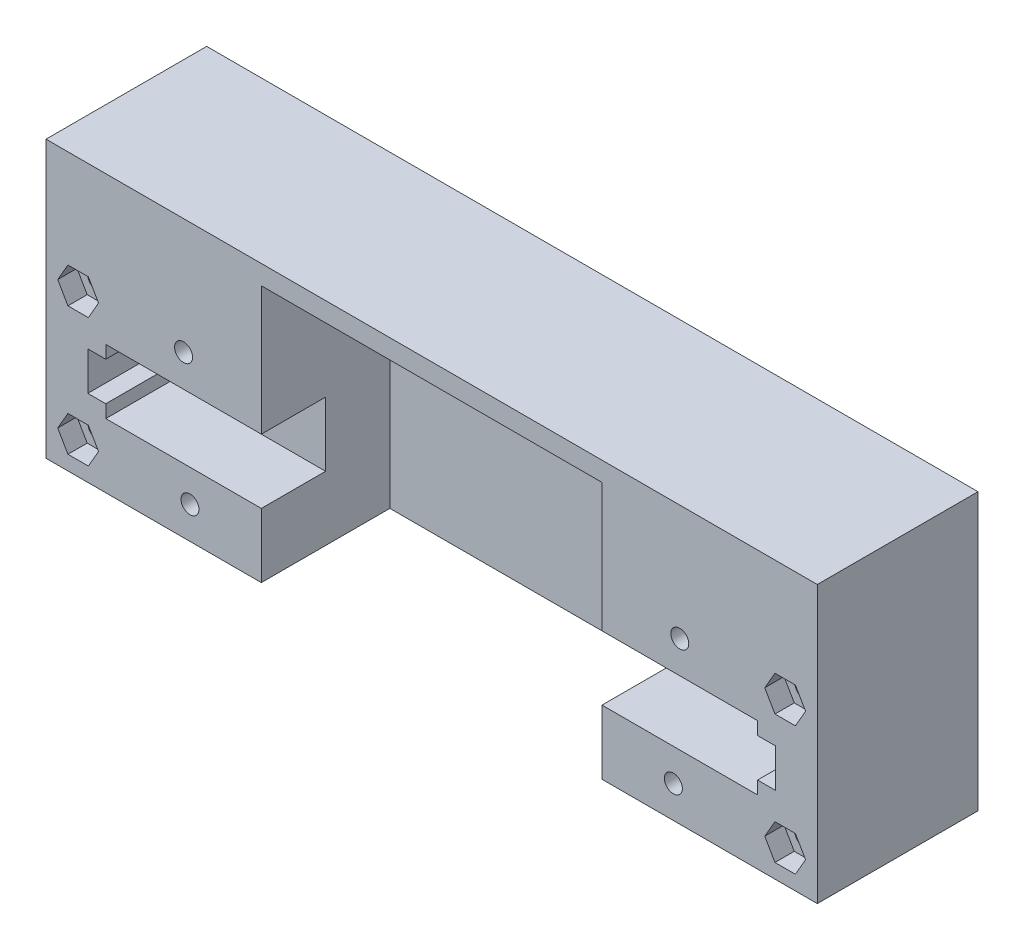
SolidWorks part; units mm, degrees
note: The reader was unsure of these and kept them because the rebuilt part matched: shared geometry of "Esquisse1<4>", "Esquisse1<5>", "Esquisse1<6>".
ref_plane "Plan de face" through (0, 0, 0) normal (0, 0, 1) x (1, 0, 0)
ref_plane "Plan de dessus" through (0, 0, 0) normal (0, 1, 0) x (1, 0, 0)
ref_plane "Plan de droite" through (0, 0, 0) normal (1, 0, 0) x (0, 0, -1)
sketch "Esquisse1" plane through (0, 0, 0) normal (0, 0, 1) x (1, 0, 0)
  line L0 (-60, 0) -> (60, 0) construction
  line L1 (-60, 15) -> (60, 15)
  line L2 (-60, 15) -> (-60, -15)
  line L3 (-60, -15) -> (60, -15)
  line L4 (60, 15) -> (60, -15)
  line L5 (-60, 15) -> (60, -15) construction
  line L6 (-60, -15) -> (60, 15) construction
  line L7 (60, 5) -> (-60, 5)
  line L8 (60, 5) -> (60, -5)
  line L9 (60, -5) -> (-60, -5)
  line L10 (-60, 5) -> (-60, -5)
  line L11 (60, 5) -> (-60, -5) construction
  line L12 (60, -5) -> (-60, 5) construction
  line L13 (26.5, 15) -> (-26.5, 15)
  line L14 (26.5, 15) -> (26.5, -15)
  line L15 (26.5, -15) -> (-26.5, -15)
  line L16 (-26.5, 15) -> (-26.5, -15)
  line L17 (26.5, 15) -> (-26.5, -15) construction
  line L18 (26.5, -15) -> (-26.5, 15) construction
  line L19 (-60, 5) -> (-53.5, 5)
  line L20 (-60, 5) -> (-60, -5)
  line L21 (-60, -5) -> (-53.5, -5)
  line L22 (-53.5, 5) -> (-53.5, -5)
  line L23 (60, 5) -> (53.5, 5)
  line L24 (60, 5) -> (60, -5)
  line L25 (60, -5) -> (53.5, -5)
  line L26 (53.5, 5) -> (53.5, -5)
  line L27 (-53.5, 5) -> (-50.7, 5)
  line L28 (-53.5, 5) -> (-53.5, 3)
  line L29 (-53.5, 3) -> (-50.7, 3)
  line L30 (-50.7, 5) -> (-50.7, 3)
  line L31 (-53.5, -3) -> (-50.7, -3)
  line L32 (-53.5, -3) -> (-53.5, -5)
  line L33 (-53.5, -5) -> (-50.7, -5)
  line L34 (-50.7, -3) -> (-50.7, -5)
  line L35 (53.5, 5) -> (50.7, 5)
  line L36 (53.5, 5) -> (53.5, 3)
  line L37 (53.5, 3) -> (50.7, 3)
  line L38 (50.7, 5) -> (50.7, 3)
  line L39 (53.5, -5) -> (50.7, -5)
  line L40 (53.5, -5) -> (53.5, -3)
  line L41 (53.5, -3) -> (50.7, -3)
  line L42 (50.7, -5) -> (50.7, -3)
  line L43 (0, 15) -> (0, -15) construction
  line L44 (-53.4123, -7.25) -> (-51.8246, -10)
  line L45 (-51.8246, 10) -> (-53.4123, 12.75)
  line L46 (-53.4123, 12.75) -> (-56.5877, 12.75)
  line L47 (-56.5877, 12.75) -> (-58.1754, 10)
  line L48 (-58.1754, 10) -> (-56.5877, 7.25)
  line L49 (-56.5877, 7.25) -> (-53.4123, 7.25)
  line L50 (-53.4123, 7.25) -> (-51.8246, 10)
  line L51 (-56.5877, -7.25) -> (-53.4123, -7.25)
  line L52 (-58.1754, -10) -> (-56.5877, -7.25)
  line L53 (-56.5877, -12.75) -> (-58.1754, -10)
  line L54 (-53.4123, -12.75) -> (-56.5877, -12.75)
  line L55 (-51.8246, -10) -> (-53.4123, -12.75)
  line L56 (56.5877, -7.25) -> (53.4123, -7.25)
  line L57 (58.1754, -10) -> (56.5877, -7.25)
  line L58 (56.5877, -12.75) -> (58.1754, -10)
  line L59 (53.4123, -12.75) -> (56.5877, -12.75)
  line L60 (51.8246, -10) -> (53.4123, -12.75)
  line L61 (53.4123, -7.25) -> (51.8246, -10)
  line L62 (53.4123, 7.25) -> (51.8246, 10)
  line L63 (56.5877, 7.25) -> (53.4123, 7.25)
  line L64 (58.1754, 10) -> (56.5877, 7.25)
  line L65 (56.5877, 12.75) -> (58.1754, 10)
  line L66 (53.4123, 12.75) -> (56.5877, 12.75)
  line L67 (51.8246, 10) -> (53.4123, 12.75)
  circle A0 centre (-55, 10) radius 1.5
  circle A1 centre (-55, -10) radius 1.5
  circle A2 centre (55, -10) radius 1.5
  circle A3 centre (55, 10) radius 1.5
  circle A4 centre (-55, 10) radius 2.75 construction
  circle A5 centre (-55, -10) radius 2.75 construction
  circle A6 centre (55, -10) radius 2.75 construction
  circle A7 centre (55, 10) radius 2.75 construction
  point P0 (0, 0)
  point P6 (0, 0)
  point P11 (0, 0)
  dimension "D9" = 55
  dimension "D11" = 3
  dimension "D1" = 120
  dimension "D2" = 30
  dimension "D3" = 10
  dimension "D4" = 53
  dimension "D5" = 27
  dimension "D6" = 27
  dimension "D7" = 24.2
  dimension "D8" = 2
  dimension "D10" = 10
extrude "Boss.-Extru.1" add sketch "Esquisse1" against normal blind 5 contours L1 L4 L3 L2 | A0 | A1 | A2 | A3
extrude "Boss.-Extru.2" add sketch "Esquisse1<4>" along normal blind 20 contours L16 L1 L2 L7 | L16 L9 L2 L3 | L9 L14 L3 L4 | L1 L14 L7 L4 | L22 L7 L2 L9 | L7 L26 L9 L4 | L28 L27 L30 L29 | L32 L31 L34 L33 | L40 L39 L42 L41 | L36 L35 L38 L37
sketch "Esquisse1<4>" plane through (0, 0, 0) normal (0, 0, 1) x (1, 0, 0) same geometry as "Esquisse1"
extrude "Boss.-Extru.3" add sketch "Esquisse1<5>" along normal blind 10 contours L16 L7 L2 L9 | L7 L14 L9 L4
sketch "Esquisse1<5>" plane through (0, 0, 0) normal (0, 0, 1) x (1, 0, 0) same geometry as "Esquisse1"
extrude "Boss.-Extru.4" add sketch "Esquisse1<6>" along normal offset from surface (17 mm away) 3 contours L67 L62 L63 L64 L65 L66 A3 | L56 L61 L60 L59 L58 L57 A2 | L49 L50 L45 L46 L47 L48 A0 | L55 L44 L51 L52 L53 L54 A1 up to face at (-55, 10, 20)
sketch "Esquisse1<6>" plane through (0, 0, 0) normal (0, 0, 1) x (1, 0, 0) same geometry as "Esquisse1"
sketch "Esquisse2" plane through (0, 0, 20) normal (0, 0, 1) x (1, 0, 0)
  line L0 (-26.5, 5) -> (-50.7, 5) construction
  line L1 (-26.5, -5) -> (-50.7, -5) construction
  line L2 (50.7, 5) -> (26.5, 5) construction
  circle A0 centre (-38.6, 10) radius 1.4
  circle A1 centre (-37.6, -10) radius 1.4
  circle A2 centre (38.6, 10) radius 1.4
  circle A3 centre (37.6, -10) radius 1.4
  point P4 (-38.6, 5)
  point P14 (38.6, 5)
  dimension "D1" = 5
  dimension "D3" = 5
  dimension "D4" = 5
  dimension "D2" = 0
extrude "Enlèv. mat.-Extru.1" cut sketch "Esquisse2" against normal through all
sketch "Esquisse3" plane through (0, 15, 0) normal (0, 1, 0) x (1, 0, 0)
  line L0 (-60, -20) -> (-60, 5)
  line L1 (-60, 5) -> (60, 5)
  line L2 (60, 5) -> (60, -20)
  line L3 (60, -20) -> (26.5, -20)
  line L4 (26.5, -20) -> (26.5, 0)
  line L5 (26.5, 0) -> (-26.5, 0)
  line L6 (-26.5, 0) -> (-26.5, -20)
  line L7 (-26.5, -20) -> (-60, -20)
extrude "Boss.-Extru.5" add sketch "Esquisse3" along normal blind 10
sketch "Esquisse4" plane through (0, 25, 0) normal (0, 1, 0) x (1, 0, 0)
  line L0 (-60, 5) -> (60, 5)
  line L1 (60, 5) -> (60, -20)
  line L2 (60, -20) -> (-60, -20)
  line L3 (-60, -20) -> (-60, 5)
extrude "Boss.-Extru.6" add sketch "Esquisse4" along normal blind 3
